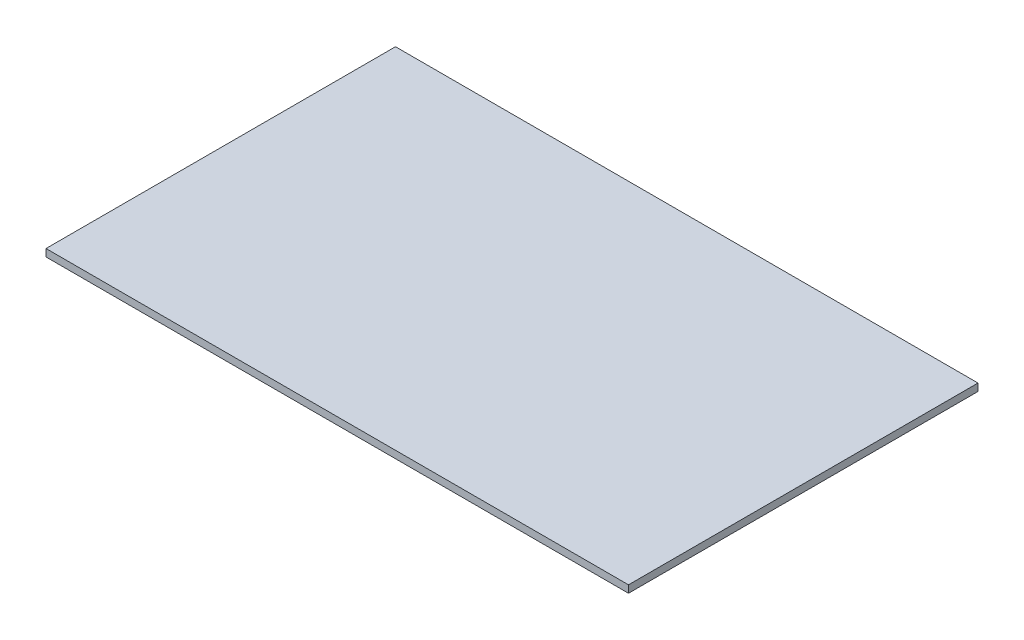
SolidWorks part; units mm, degrees
ref_plane "Front" through (0, 0, 0) normal (0, 0, 1) x (1, 0, 0)
ref_plane "Top" through (0, 0, 0) normal (0, 1, 0) x (1, 0, 0)
ref_plane "Right" through (0, 0, 0) normal (1, 0, 0) x (0, 0, -1)
sketch "Sketch1" plane through (0, 0, 0) normal (0, 1, 0) x (1, 0, 0)
  line L1 (-63.5, -38.1) -> (63.5, -38.1)
  line L2 (-63.5, -38.1) -> (-63.5, 38.1)
  line L3 (-63.5, 38.1) -> (63.5, 38.1)
  line L4 (63.5, -38.1) -> (63.5, 38.1)
  line L5 (-63.5, -38.1) -> (63.5, 38.1) construction
  line L6 (-63.5, 38.1) -> (63.5, -38.1) construction
  point P0 (0, 0)
  dimension "D1" = 127
  dimension "D2" = 76.2
extrude "Boss-Extrude1" add sketch "Sketch1" along normal blind 1.6
